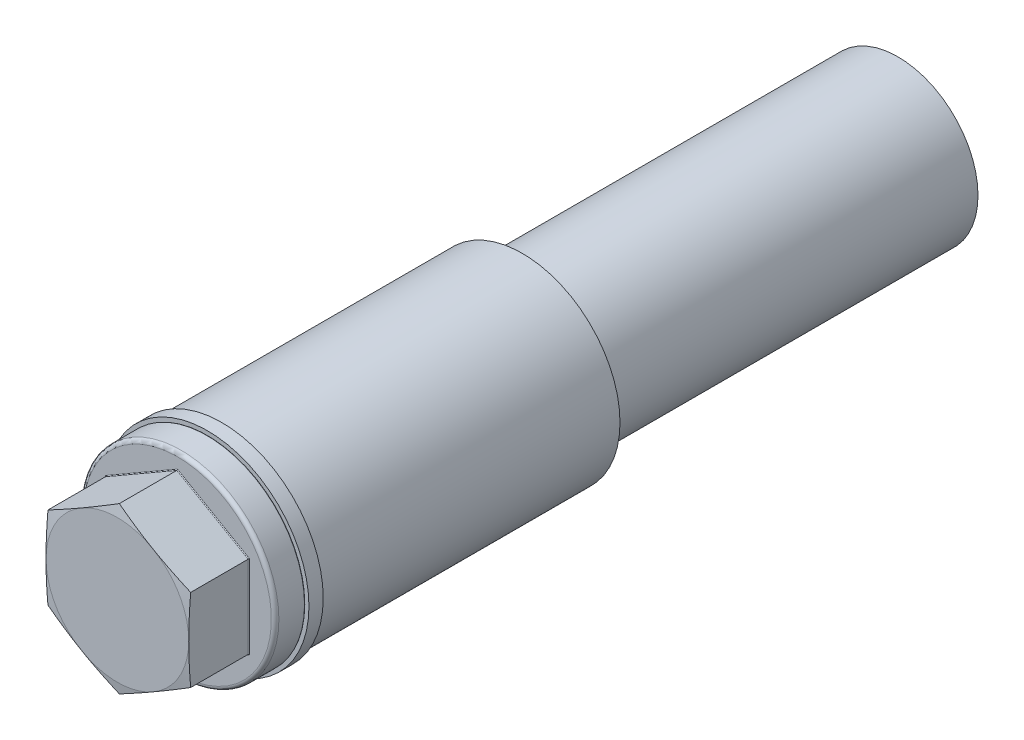
SolidWorks part; units mm, degrees
material "MS EN 10025"
ref_plane "Front Plane" through (0, 0, 0) normal (0, 0, 1) x (1, 0, 0)
ref_plane "Top Plane" through (0, 0, 0) normal (0, 1, 0) x (1, 0, 0)
ref_plane "Right Plane" through (0, 0, 0) normal (1, 0, 0) x (0, 0, -1)
sketch "Sketch1" plane through (0, 0, 0) normal (1, 0, 0) x (0, 0, -1)
  line L0 (0, 0) -> (26, 0) construction
  line L1 (0, 9.5) -> (0, -9.5) construction
  line L2 (12, 13) -> (12, -13) construction
  line L3 (26, 10.4) -> (26, -10.4) construction
  line L4 (13, 10.5) -> (13, -10.5) construction
  line L5 (13, 10.5) -> (13, 12.5) construction
  line L6 (13, 13) -> (13, -13) construction
  point P5 (0, 0)
  point P6 (12, 0)
  point P7 (12, 0)
  point P10 (8, 0)
  point P11 (12, 0)
  point P14 (26, 0)
  point P15 (13, 0)
  point P16 (13, 0)
  point P19 (13, 0)
  point P23 (13, 0)
  point P24 (15, 0)
  dimension "D1" = 1
sketch "Sketch2" plane through (0, 0, 0) normal (0, 0, 1) x (1, 0, 0)
  line L1 (0, -10.9697) -> (9.5, -5.4848)
  line L2 (9.5, -5.4848) -> (9.5, 5.4848)
  line L3 (9.5, 5.4848) -> (0, 10.9697)
  line L4 (0, 10.9697) -> (-9.5, 5.4848)
  line L5 (-9.5, 5.4848) -> (-9.5, -5.4848)
  line L6 (-9.5, -5.4848) -> (0, -10.9697)
  circle A0 centre (0, 0) radius 9.5 construction
extrude "Boss-Extrude1" add sketch "Sketch2" against normal up to vertex (8 mm away) up to point (0, 0, -8)
sketch "Sketch3" plane through (0, 0, 0) normal (0, 0, 1) x (1, 0, 0)
  line L0 (0, 13) -> (0, -13) construction
  line L1 (0, 10.9697) -> (-9.5, 5.4848) construction
  circle A0 centre (0, 0) radius 9.5
extrude "Cut-Extrude1" cut sketch "Sketch3" against normal through all draft 80 flip side to cut
sketch "Sketch4" plane through (0, 0, -8) normal (0, 0, -1) x (-1, 0, 0)
  circle A0 centre (0, 0) radius 13
extrude "Boss-Extrude2" add sketch "Sketch4" along normal up to vertex (4 mm away) up to point (0, 0, -12)
fillet "Fillet1" radius 0.5 1 edges at (-13, 0, -8)
sketch "Sketch5" plane through (0, 0, 0) normal (1, 0, 0) x (0, 0, -1)
  line L0 (12, 10.9697) -> (12, 0)
  line L2 (12, 0) -> (26, 0)
  line L3 (26, 0) -> (26, 9.0393)
  line L4 (26, 9.0393) -> (24.6393, 10.4)
  line L5 (24.6393, 10.4) -> (15.0411, 10.4)
  line L6 (15.0411, 10.4) -> (13.6804, 9.0393)
  line L7 (13.6804, 9.0393) -> (13, 9.0393)
  line L8 (13, 9.0393) -> (12, 10.9697)
  dimension "D1" = 45
  dimension "D2" = 45
  dimension "D4" = 1.3607
  dimension "D3" = 0.6804
revolve "Revolve1" add sketch "Sketch5" angle 360 about L2
ref_plane "Plane1" through (0, 0, -13) normal (0, 0, 1) x (1, 0, 0)
fillet "Fillet2" radius 0.1 7 edges at (4.75, -8.2272, -8) (9.5, 0, -8) (4.75, 8.2272, -8) (-4.75, 8.2272, -8) (-9.5, 0, -8) (-4.75, -8.2272, -8) (-13, 0, -12)
sketch "Sketch8" plane through (0, 0, 0) normal (1, 0, 0) x (0, 0, -1)
  line L0 (0, 0) -> (26, 0) construction
  line L1 (13, 13) -> (15, 13)
  line L2 (13, 13) -> (13, 10.5)
  line L3 (13, 10.5) -> (15, 10.5)
  line L4 (15, 13) -> (15, 10.5)
  line L5 (0, 0) -> (26, 0) construction
revolve "Revolve2" [suppressed] add sketch "Sketch8" angle 360 about L5
fillet "Fillet3" [suppressed] radius 0.2
split "Split1" trim tools "Plane1" bodies to split 105 resulting bodies 108 109
sketch "Sketch6" plane through (0, 0, -26) normal (0, 0, -1) x (-1, 0, 0)
  circle A0 centre (0, 0) radius 10.4
curve "Helix/Spiral1" pitch 1.8143 height 14 radius 10.4 centre (0, 0, -26) axis (0, 0, 1) start towards (0, 1, 0) parameters "Pitch"=1.8143
sketch "Sketch7" plane through (0, 0, 0) normal (1, 0, 0) x (0, 0, -1)
  line L0 (25.974, 10.45) -> (27.6135, 10.45)
  line L1 (27.6135, 10.45) -> (27.5875, 10.4)
  line L2 (27.5875, 10.4) -> (26.9071, 9.093)
  line L3 (26.9071, 9.093) -> (26.6804, 9.093)
  line L4 (26.6804, 9.093) -> (26, 10.4)
  line L5 (26, 10.4) -> (25.974, 10.45)
  line L6 (26, 10.4) -> (27.5875, 10.4) construction
  line L7 (26.7937, 10.45) -> (26.7937, 9.093) construction
  line L8 (26.3402, 9.7465) -> (27.2473, 9.7465) construction
  dimension "D1" = 0.05
  dimension "D2" = 55
  dimension "D3" = 0.9071
  dimension "D4" = 0.2268
sweep "Cut-Sweep1" cut profiles "Sketch7" path "Helix/Spiral1" align with end faces yes
combine bodies "Combine1" operation type add bodies to combine 108 107
ref_axis "Center Axis 1" through (0, 0, -2.162) along (0, 0, 1)
ref_plane "Contact Plane 1" through (0, 0, -12) normal (0, 0, -1) x (-1, 0, 0)
sketch "Sketch9" plane through (0, 0, 0) normal (1, 0, 0) x (0, 0, -1)
  line L0 (0, 0) -> (76.5013, 0) construction
  line L1 (13.9, 9.3155) -> (43.9, 9.3155)
  line L2 (43.9, 9.3155) -> (43.9, 7.85)
  line L3 (43.9, 7.85) -> (101.131, 7.85)
  line L4 (101.131, 7.85) -> (101.131, 0)
  line L5 (101.131, 0) -> (103.9, 0)
  line L6 (103.9, 0) -> (103.9, 10.65)
  line L7 (103.9, 10.65) -> (53.9, 10.65)
  line L8 (53.9, 10.65) -> (53.9, 13)
  line L9 (53.9, 13) -> (13.9, 13)
  line L10 (13.9, 13) -> (13.9, 9.3155)
  line L11 (11.9, -13) -> (11.9, 13) construction
  dimension "D1" = 26
  dimension "D2" = 40
  dimension "D3" = 90
  dimension "D4" = 21.3
  dimension "D5" = 15.7
  dimension "D6" = 18.631
  dimension "D7" = 2.769
  dimension "D8" = 30
  dimension "D9" = 2
revolve "Thermometer case" add sketch "Sketch9" angle 360 about L0
sketch "Sketch10" plane through (0, 0, 0) normal (0, 1, 0) x (1, 0, 0)
  line L0 (0, 0.2591) -> (0, 33.6486) construction
  line L1 (-13, 13.9) -> (13, 13.9) construction
  line L2 (-9.5, 13.9) -> (-13.5, 13.9)
  line L3 (-9.5, 13.9) -> (-9.5, 12)
  line L4 (-9.5, 12) -> (-13.5, 12)
  line L5 (-13.5, 13.9) -> (-13.5, 12)
  line L6 (12.9, 12) -> (-12.9, 12) construction
  dimension "D1" = 19
  dimension "D2" = 27
revolve "Gasket" add sketch "Sketch10" angle 360 about L0
equation "\"D3@Helix/Spiral1\"=\"Thread Length@Sketch1\""
equation "\"D3@Sketch7\"=\"Pitch@Helix/Spiral1\"/2"
equation "\"D4@Sketch7\"=\"Pitch@Helix/Spiral1\"/8"
equation "\"D4@Sketch5\"=\"Pitch@Helix/Spiral1\"*.75"
equation "\"D3@Sketch5\"=\"D4@Sketch5\"/2"
equation "\"D1@Fillet3\"=\"Washer Thickness@Sketch1\"*.1"
